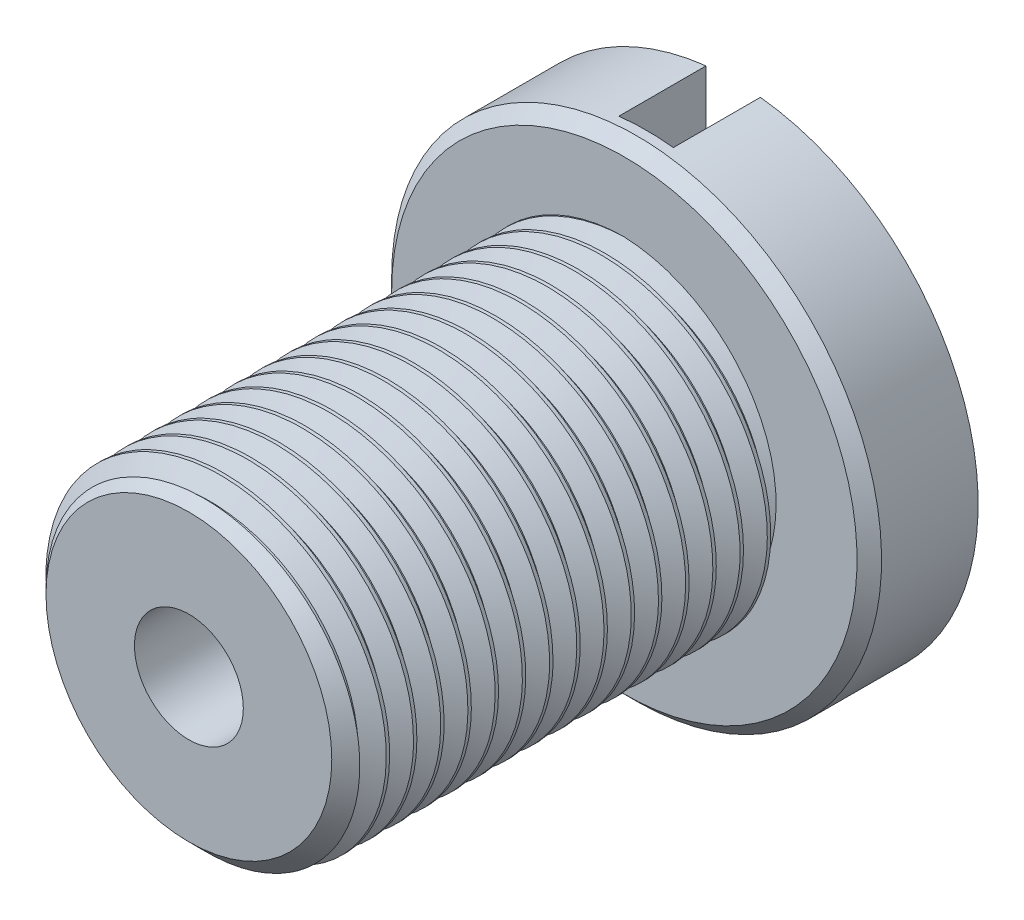
SolidWorks part; units mm, degrees
ref_plane "Front Plane" through (0, 0, 0) normal (0, 0, 1) x (1, 0, 0)
ref_plane "Top Plane" through (0, 0, 0) normal (0, 1, 0) x (1, 0, 0)
ref_plane "Right Plane" through (0, 0, 0) normal (1, 0, 0) x (0, 0, -1)
sketch "Sketch0" plane through (0, 0, 0) normal (1, 0, 0) x (0, 0, -1)
  line L0 (0, 0) -> (25.4, 0) construction
  point P2 (44.45, 0)
  point P4 (0, 0)
  dimension "D1" = 25.4
  dimension "D2" = 19.05
  dimension "Min Thread" = 0
sketch "Sketch1" plane through (0, 0, 0) normal (0, 0, 1) x (1, 0, 0)
  circle A0 centre (0, 0) radius 9.525
  dimension "OD" = 19.05
extrude "Extrude1" add sketch "Sketch1" against normal blind 25.4
sketch "Sketch2" plane through (0, 0, 0) normal (0, 0, 1) x (1, 0, 0)
  circle A0 centre (0, 0) radius 9.525 construction
  circle A1 centre (0, 0) radius 9.525
curve "Helix/Spiral1" pitch 1.5875 height 26.9875 turns 17 parameters "pitch"=1.5875
chamfer "Chamfer3" distance 1.1906 angle 45 1 edges at (9.525, 0, 0)
sketch "Sketch3" plane through (0, 0, 0) normal (1, 0, 0) x (0, 0, -1)
  line L0 (-1.3891, 9.525) -> (-0.7938, 8.4939)
  line L1 (-0.7938, 8.4939) -> (-0.5953, 8.4939)
  line L2 (-0.5953, 8.4939) -> (0, 9.525)
  line L3 (-1.3891, 9.525) -> (0, 9.525)
  line L4 (-0.6945, 9.525) -> (-0.6945, 8.4939) construction
  line L5 (-1.0914, 9.0094) -> (-0.2977, 9.0094) construction
  line L6 (0, 9.525) -> (0, -9.525) construction
  dimension "D1" = 0.1984
  dimension "D2" = 0.7937
  dimension "D3" = 60
sweep "Cut-Sweep1" cut profiles "Sketch3" path "Helix/Spiral1"
sketch "Sketch5" plane through (0, 0, 0) normal (1, 0, 0) x (0, 0, -1)
  line L0 (25.4, -8.5034) -> (25.4, 6.7963) construction
  line L1 (25.4, 9.525) -> (0, 9.525)
  line L2 (25.4, 9.525) -> (25.4, 0)
  line L3 (25.4, 0) -> (-3.4668, 0)
  line L4 (0, 0) -> (25.4, 0) construction
  line L5 (0, 9.525) -> (-3.4668, 0)
  line L6 (0, 0) -> (27.94, 0) construction
  dimension "D1" = 70
  dimension "D3" = 2.54
revolve "partially thread" [suppressed] add sketch "Sketch5" angle 360 about L6
sketch "Sketch6" plane through (0, 0, -25.4) normal (0, 0, -1) x (-1, 0, 0)
  circle A0 centre (0, 0) radius 14.2875
  dimension "head dia" = 28.575
extrude "Extrude2" add sketch "Sketch6" along normal blind 19.05
sketch "Sketch7" plane through (0, 0, -44.45) normal (0, 0, -1) x (-1, 0, 0)
  line L1 (0, 9.1654) -> (-7.9375, 4.5827)
  line L2 (-7.9375, 4.5827) -> (-7.9375, -4.5827)
  line L3 (-7.9375, -4.5827) -> (0, -9.1654)
  line L4 (0, -9.1654) -> (7.9375, -4.5827)
  line L5 (7.9375, -4.5827) -> (7.9375, 4.5827)
  line L6 (7.9375, 4.5827) -> (0, 9.1654)
  circle A0 centre (0, 0) radius 7.9375 construction
  dimension "hex dia" = 15.875
extrude "Cut-Extrude1" cut sketch "Sketch7" against normal blind 11.9062
sketch "Sketch8" plane through (0, 0, -44.45) normal (0, 0, -1) x (-1, 0, 0)
  circle A0 centre (0, 0) radius 9.1654
extrude "Cut-Extrude2" cut sketch "Sketch8" against normal through all draft 45
chamfer "Chamfer1" distance 1.4287 angle 45 1 edges at (-14.2875, 0, -44.45)
chamfer "Chamfer2" distance 0.7144 angle 45 1 edges at (-14.2875, 0, -25.4)
sketch "Sketch9" plane through (0, 0, 0) normal (1, 0, 0) x (0, 0, -1)
  line L0 (0, 9.525) -> (0, -9.525) construction
  line L1 (3.9687, 9.525) -> (3.9688, -9.525) construction
  line L2 (44.45, 14.2875) -> (44.45, -14.2875) construction
  line L3 (25.4, 14.2875) -> (25.4, -14.2875) construction
  line L4 (25.4, 13.5731) -> (25.4, -13.5731) construction
  line L5 (44.45, -12.8588) -> (44.45, 12.8588) construction
  line L6 (25.4, -14.2875) -> (25.4, 14.2875) construction
  line L7 (0, 8.3344) -> (0, -8.3344) construction
  line L8 (-1.3891, 9.525) -> (0, 9.525) construction
  line L9 (3.9688, 0) -> (0, 0) construction
  dimension "D1" = 3.9688
sketch "Sketch11" plane through (0, 0, -44.45) normal (0, 0, -1) x (-1, 0, 0)
  circle A0 centre (0, 0) radius 17.3473
extrude "Cut-Extrude4" cut sketch "Sketch11" against normal blind 12.7
sketch "Sketch13" plane through (0, 0, -31.75) normal (0, 0, -1) x (-1, 0, 0)
  circle A0 centre (0, 0) radius 3.175
  dimension "D1" = 6.35
extrude "Cut-Extrude6" cut sketch "Sketch13" against normal through all
sketch "Sketch15" plane through (0, 0, -31.75) normal (0, 0, -1) x (-1, 0, 0)
  line L0 (-1.5875, 15.24) -> (1.5875, -15.24) construction
  line L1 (-1.5875, 15.24) -> (1.5875, 15.24)
  line L2 (-1.5875, 15.24) -> (-1.5875, -15.24)
  line L3 (-1.5875, -15.24) -> (1.5875, -15.24)
  line L4 (1.5875, 15.24) -> (1.5875, -15.24)
  line L5 (-1.5875, -15.24) -> (1.5875, 15.24) construction
  point P4 (0, 0)
  dimension "D1" = 30.48
  dimension "D2" = 3.175
extrude "Cut-Extrude7" cut sketch "Sketch15" against normal blind 5.08
equation "\"D3@Helix/Spiral1\" = \"screw length@Extrude1\"+\"pitch@Helix/Spiral1\""
equation "\"D1@Sketch3\" = \"pitch@Helix/Spiral1\"*.125"
equation "\"D2@Sketch3\" = \"pitch@Helix/Spiral1\"*.5"
equation "\"D1@Cut-Extrude1\" = \"hex dia@Sketch7\"*.75"
equation "\"D1@Chamfer1\" = \"head dia@Sketch6\"*.05"
equation "\"D1@Sketch9\" = \"pitch@Helix/Spiral1\"*2.50"
equation "\"D1@Chamfer2\" = \"D1@Chamfer1\"/2"
equation "\"D1@Chamfer3\" = \"pitch@Helix/Spiral1\"*.750"
equation "\"D1@Sketch0\" = \"screw length@Extrude1\""
equation "\"D2@Sketch0\" = \"head depth@Extrude2\""
